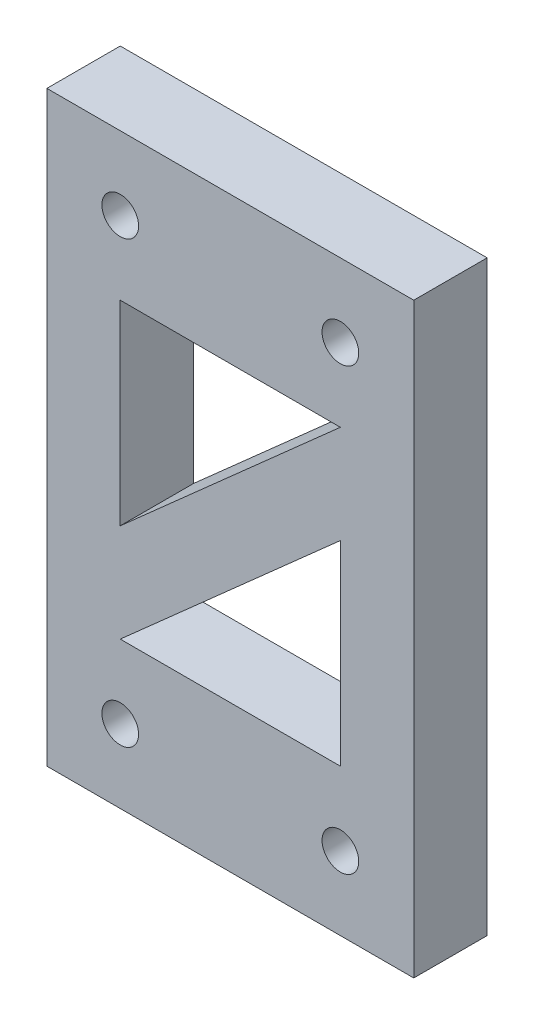
SolidWorks part; units mm, degrees
ref_plane "Front Plane" through (0, 0, 0) normal (0, 0, 1) x (1, 0, 0)
ref_plane "Top Plane" through (0, 0, 0) normal (0, 1, 0) x (1, 0, 0)
ref_plane "Right Plane" through (0, 0, 0) normal (1, 0, 0) x (0, 0, -1)
sketch "Sketch1" plane through (0, 0, 0) normal (0, 0, 1) x (1, 0, 0)
  line L1 (0, 0) -> (50, 0)
  line L2 (0, 0) -> (0, 80)
  line L3 (0, 80) -> (50, 80)
  line L4 (50, 0) -> (50, 80)
  dimension "D1" = 80
  dimension "D2" = 50
base flange "Base-Flange1" sketch "Sketch1" thickness 10 reverse thickness direction no parameters "D1"=0.7366
sketch "Sketch6" plane through (0, 0, 0) normal (0, 0, 1) x (1, 0, 0)
  line L0 (50, 0) -> (50, 80) construction
  line L1 (50, 80) -> (0, 80) construction
  line L2 (0, 40) -> (50, 40) construction
  line L4 (40, 46.6288) -> (40, 20)
  line L5 (40, 20) -> (10, 20)
  line L6 (10, 20) -> (40, 46.6288)
  line L7 (40, 60) -> (10, 33.3712)
  line L8 (10, 33.3712) -> (10, 60)
  line L9 (10, 60) -> (40, 60)
  line L10 (0, 80) -> (0, 0) construction
  circle A0 centre (40, 70) radius 2.5
  circle A1 centre (10, 10) radius 2.5
  circle A2 centre (10, 70) radius 2.5
  circle A3 centre (40, 10) radius 2.5
  dimension "D1" = 5
  dimension "D2" = 10
  dimension "D3" = 10
  dimension "D4" = 60
  dimension "D5" = 30
  dimension "D6" = 10
  dimension "D7" = 10
  dimension "D8" = 10
  dimension "D10" = 10
extrude "Cut-Extrude1" cut sketch "Sketch6" against normal up to next normal cut yes
sketch "Bend-Lines1" plane through (0, 0, 0) normal (0, 1, 0) x (1, 0, 0)
sketch "Bounding-Box1" plane through (0, 0, 0) normal (0, 1, 0) x (1, 0, 0)
sheet metal parameters "Sheet-Metal1" thickness 10 parameters "D1"=0.7366
flat pattern "Flat-Pattern1" [suppressed]
sketch "Bend-Lines2" plane through (0, 0, 0) normal (0, 1, 0) x (1, 0, 0)
sketch "Bounding-Box2" [suppressed] plane through (0, 0, 0) normal (0, 1, 0) x (1, 0, 0)
sheet metal parameters "Sheet-Metal2" thickness 10 parameters "D1"=0.7366
flat pattern "Flat-Pattern1"
sketch "Bend-Lines2" plane through (0, 0, 0) normal (0, 1, 0) x (1, 0, 0)
sketch "Bounding-Box2" [suppressed] plane through (0, 0, 0) normal (0, 1, 0) x (1, 0, 0)
